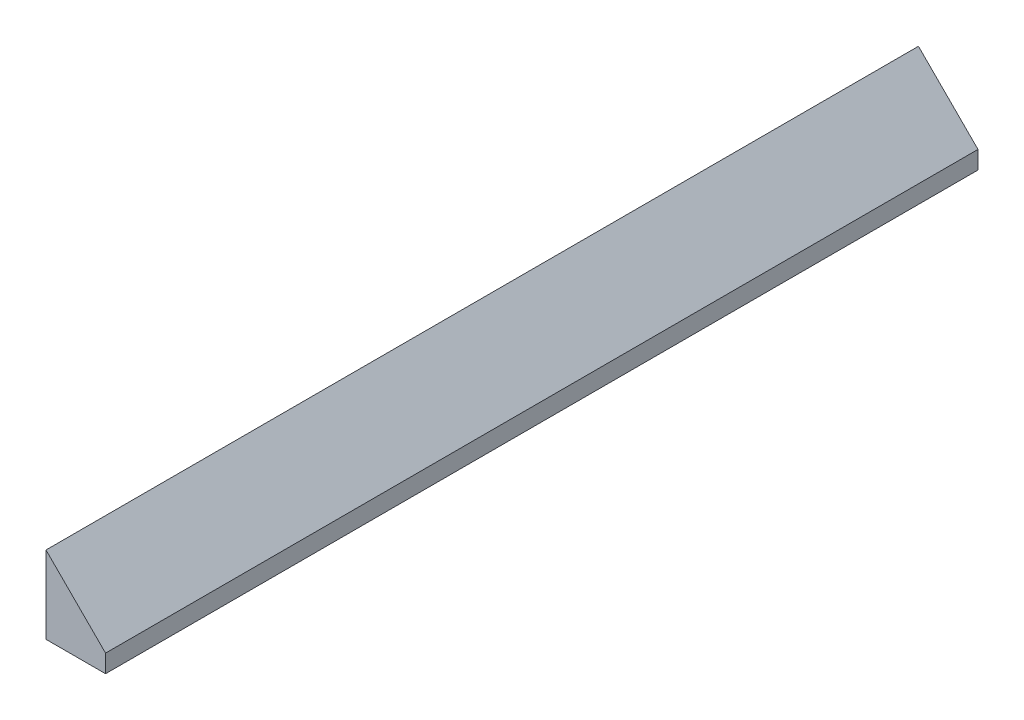
SolidWorks part; units mm, degrees
material "6061-T6 (SS)"
ref_plane "Front Plane" through (0, 0, 0) normal (0, 0, 1) x (1, 0, 0)
ref_plane "Top Plane" through (0, 0, 0) normal (0, 1, 0) x (1, 0, 0)
ref_plane "Right Plane" through (0, 0, 0) normal (1, 0, 0) x (0, 0, -1)
sketch "Sketch1" plane through (0, 0, 0) normal (0, 0, 1) x (1, 0, 0)
  line L5 (0, 0) -> (2.6, 0)
  line L6 (2.6, 0) -> (0, 2.6)
  line L7 (0, 2.6) -> (0, 0)
  line L11 (2, 0) -> (2, 0.6)
  dimension "D1" = 0.6
  dimension "D2" = 2.6
extrude "Boss-Extrude1" add sketch "Sketch1" against normal mid plane 29.3 contours L5 L11 L6 L7 region at (0.7917, 0.9042, 0)
